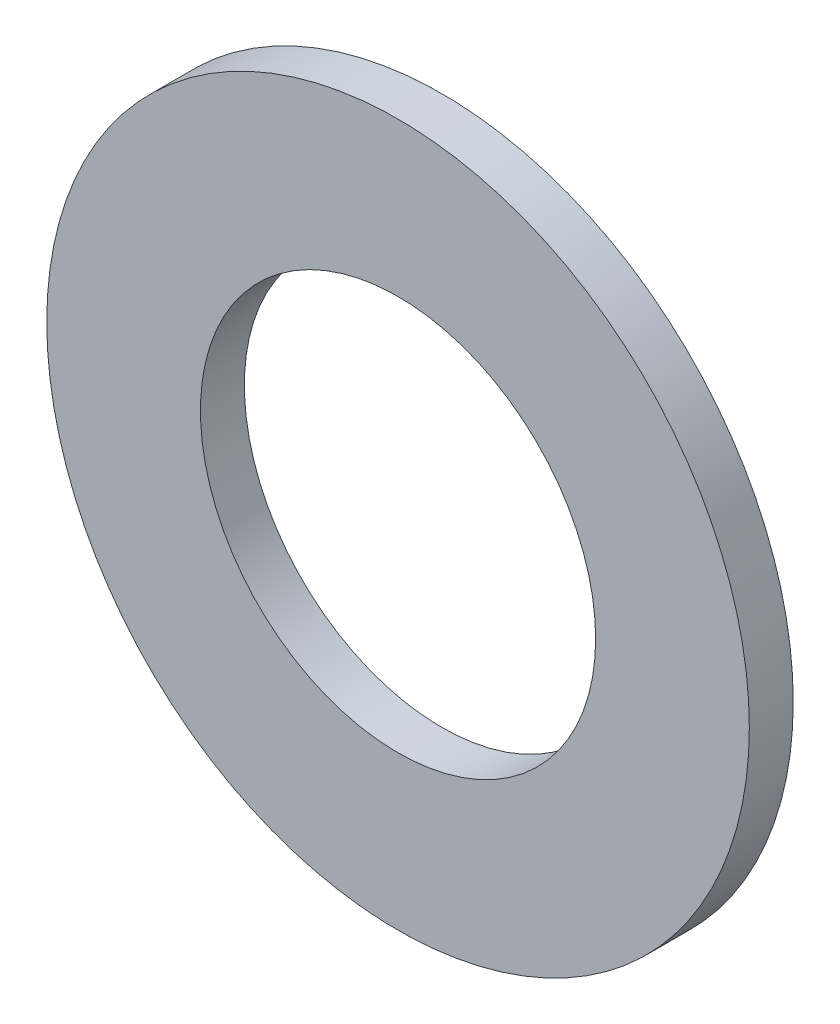
SolidWorks part; units mm, degrees
material "Латунь"
ref_plane "Спереди" through (0, 0, 0) normal (0, 0, 1) x (1, 0, 0)
ref_plane "Сверху" through (0, 0, 0) normal (0, 1, 0) x (1, 0, 0)
ref_plane "Справа" through (0, 0, 0) normal (1, 0, 0) x (0, 0, -1)
sketch "Эскиз1" plane through (0, 0, 0) normal (0, 0, 1) x (1, 0, 0)
  circle A0 centre (0, 0) radius 8
  circle A1 centre (0, 0) radius 4.5
  dimension "D1" = 9
  dimension "D2" = 16
extrude "Бобышка-Вытянуть1" add sketch "Эскиз1" along normal blind 1
equation "\"Внутренний диаметр\"= 8  '!!!"
equation "\"Внешний диаметр\"= 16"
equation "\"Толщина\"= 1  'Толщина шайбы между пластиной прижима и несущей пластиной"
equation "\"D1@Эскиз1\"=\"Внутренний диаметр\"+1"
equation "\"D1@Бобышка-Вытянуть1\"=\"Толщина\""
equation "\"D2@Эскиз1\"=\"Внешний диаметр\""
